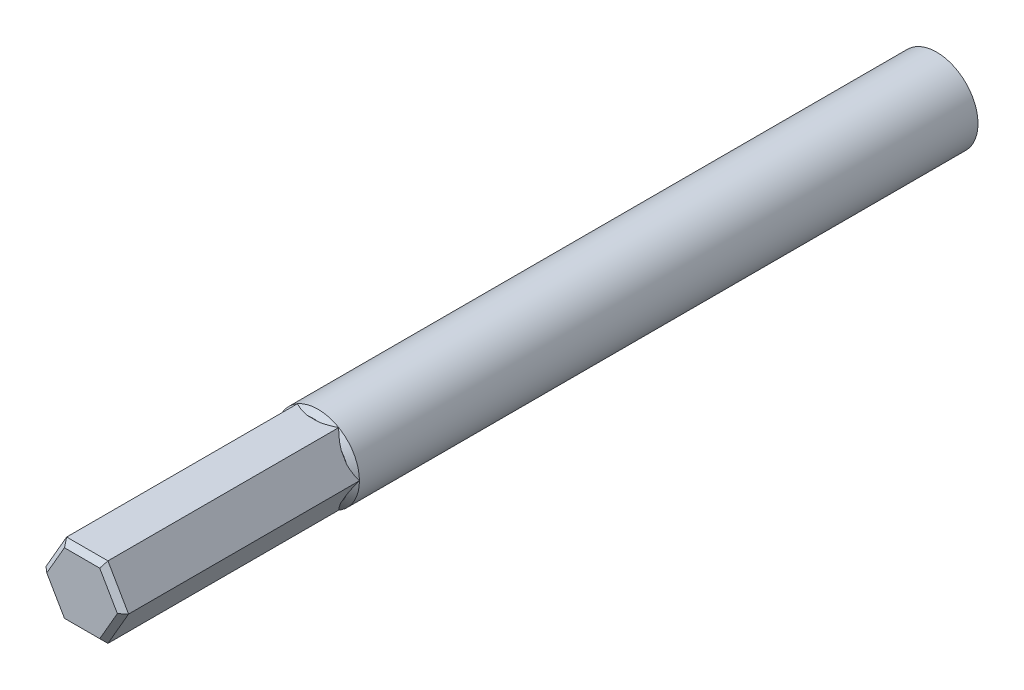
SolidWorks part; units mm, degrees
material "PETG"
ref_plane "Front Plane" through (0, 0, 0) normal (0, 0, 1) x (1, 0, 0)
ref_plane "Top Plane" through (0, 0, 0) normal (0, 1, 0) x (1, 0, 0)
ref_plane "Right Plane" through (0, 0, 0) normal (1, 0, 0) x (0, 0, -1)
sketch "Sketch1" plane through (0, 0, 0) normal (0, 0, 1) x (1, 0, 0)
  circle A0 centre (0, 0) radius 3.975
  dimension "Shaft Dia" = 7.95
extrude "Boss-Extrude1" add sketch "Sketch1" along normal blind 60
sketch "Sketch2" plane through (0, 0, 60) normal (0, 0, 1) x (1, 0, 0)
  line L1 (4, 0) -> (2, 3.4641) construction
  line L2 (2, 3.4641) -> (-2, 3.4641) construction
  line L3 (-2, 3.4641) -> (-4, 0) construction
  line L4 (-4, 0) -> (-2, -3.4641) construction
  line L5 (-2, -3.4641) -> (2, -3.4641) construction
  line L6 (2, -3.4641) -> (4, 0) construction
  line L7 (3.9711, 0) -> (1.9856, 3.4391)
  line L8 (1.9856, 3.4391) -> (-1.9856, 3.4391)
  line L9 (-1.9856, 3.4391) -> (-3.9711, 0)
  line L10 (-3.9711, 0) -> (-1.9856, -3.4391)
  line L11 (-1.9856, -3.4391) -> (1.9856, -3.4391)
  line L12 (1.9856, -3.4391) -> (3.9711, 0)
  circle A0 centre (0, 0) radius 3.4641 construction
  circle A1 centre (0, 0) radius 3.4391 construction
  dimension "Hex Circumscribed Nominal Dia" = 8
  dimension "Hex Flat To Flat Offset" = 0.025
extrude "Boss-Extrude2" add sketch "Sketch2" along normal blind 22.2
chamfer "Chamfer1" distance 0.5 angle 45 7 edges at (0, -3.4391, 82.2) (-2.9783, -1.7196, 82.2) (-2.9783, 1.7196, 82.2) (0, 3.4391, 82.2) (2.9783, 1.7196, 82.2) (2.9783, -1.7196, 82.2) (3.975, 0, 60)
equation "\"tol_dia_id_intfc\" = 0.0500mm ' For hole diameters - Interference fit"
equation "\"tol_dia_id_slip\"  = 0.0750mm ' For hole diameters - Slip fit"
equation "\"tol_dia_id_clear\" = 0.1000mm ' For hole diameters - Clearance fit"
equation "\"tol_dia_od_intfc\" = 0.0500mm ' For shaft diameters - Interference fit"
equation "\"tol_dia_od_slip\"  = 0.0750mm ' For shaft diameters - Slip fit"
equation "\"tol_dia_od_clear\" = 0.1000mm ' For shaft diameters - Clearance fit"
equation "\"tol_general_intfc\"= 0.0250mm ' For general parts (Horiz) - Interference fit"
equation "\"tol_general_slip\" = 0.0375mm ' For general parts (Horiz) - Slip fit"
equation "\"tol_general_clear\"= 0.0500mm ' For general parts (Horiz) - Clearance fit"
equation "\"tol_layer_intfc\"  = 0.0250mm ' For all parts (Vert) - Interference fit"
equation "\"tol_layer_slip\"   = 0.0375mm ' For all parts (Vert) - Slip fit"
equation "\"tol_layer_clear\"  = 0.0500mm ' For all parts (Vert) - Clearance fit"
equation "\"tol_corner_rad\"   = 0.100mm ' For corners that fit into other parts"
equation "\"Shaft Dia@Sketch1\" = \"nominal_dia\" - \"tol_dia_od_intfc\""
equation "\"nominal_dia\"= 8.00mm"
equation "\"Hex Circumscribed Nominal Dia@Sketch2\" = \"nominal_dia\""
equation "\"Hex Flat To Flat Offset@Sketch2\" = \"tol_general_intfc\""
equation "\"D1@Fillet1\"=\"tol_corner_rad\""
